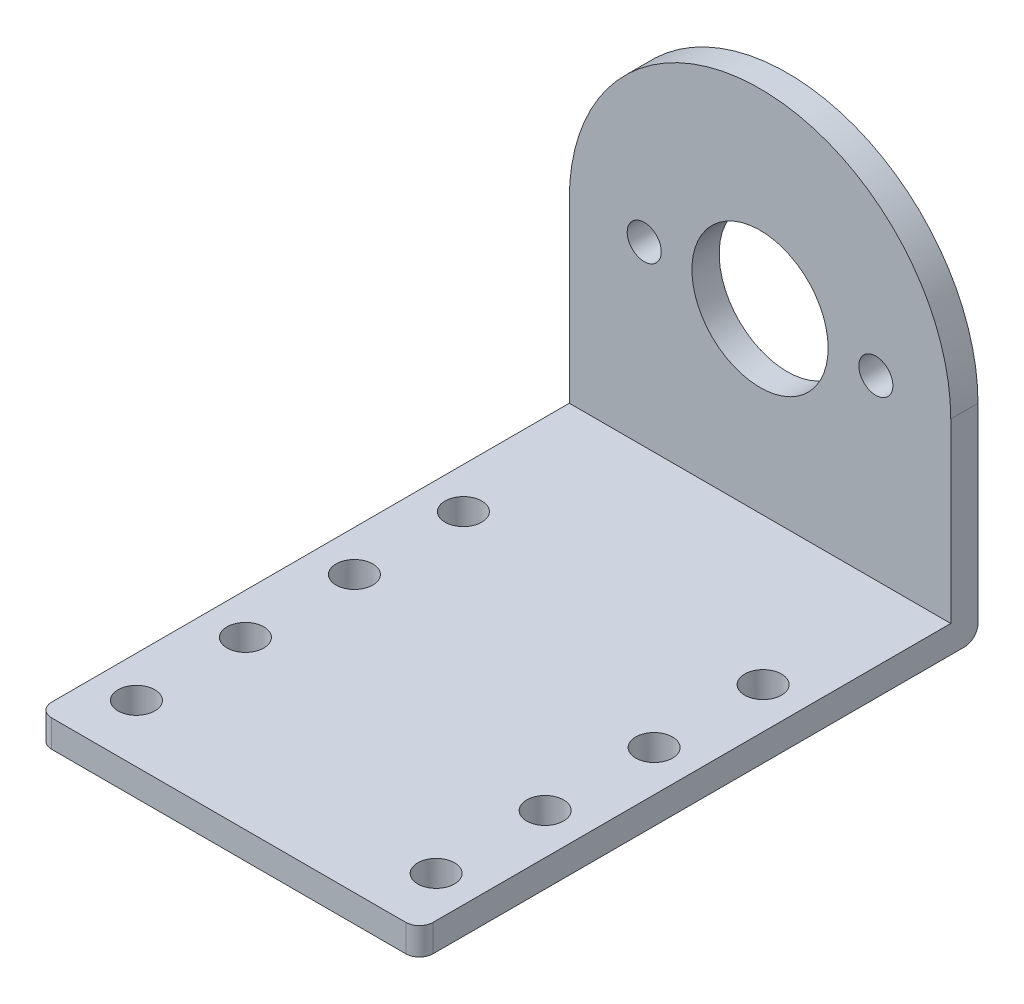
SolidWorks part; units mm, degrees
ref_plane "Front Plane" through (0, 0, 0) normal (0, 0, 1) x (1, 0, 0)
ref_plane "Top Plane" through (0, 0, 0) normal (0, 1, 0) x (1, 0, 0)
ref_plane "Right Plane" through (0, 0, 0) normal (1, 0, 0) x (0, 0, -1)
sketch "Sketch1" plane through (0, 0, 0) normal (0, 0, 1) x (1, 0, 0)
  line L0 (0, 0) -> (-8.5, 0) construction
  line L1 (0, 0) -> (8.5, 0) construction
  line L2 (-14, 0) -> (-14, -15)
  line L3 (14, 0) -> (14, -15)
  line L4 (14, -15) -> (-14, -15)
  arc A0 (14, 0) -> (-14, 0) centre (0, 0) ccw
  circle A1 centre (0, 0) radius 5
  circle A2 centre (-8.5, 0) radius 1.25
  circle A3 centre (8.5, 0) radius 1.25
  dimension "D1" = 28
  dimension "D2" = 10
  dimension "D3" = 2.5
  dimension "D5" = 2.5
  dimension "D4" = 8.5
  dimension "D6" = 8.5
  dimension "D7" = 15
extrude "Boss-Extrude1" add sketch "Sketch1" along normal blind 2
sketch "Sketch2" plane through (0, 0, 2) normal (0, 0, 1) x (1, 0, 0)
  line L0 (14, -15) -> (14, 0) construction
  line L1 (-14, -15) -> (14, -15)
  line L2 (-14, -15) -> (-14, -13)
  line L3 (-14, -13) -> (14, -13)
  line L4 (14, -15) -> (14, -13)
  dimension "D1" = 2
extrude "Boss-Extrude2" add sketch "Sketch2" along normal blind 39
fillet "Fillet1" radius 1 3 edges at (14, -14, 41) (-14, -14, 41) (0, -15, 0)
sketch "Sketch3" plane through (0, -13, 0) normal (0, 1, 0) x (1, 0, 0)
  line L0 (0, 0) -> (0, -12.7736) construction
  line L1 (-11, -12.7736) -> (0, -12.7736) construction
  line L2 (-11, -12.7736) -> (-11, -36.7736) construction
  line L3 (0, -12.7736) -> (0, -41) construction
  line L4 (13, -41) -> (-13, -41) construction
  circle A0 centre (-11, -12.7736) radius 1.35
  circle A1 centre (-11, -36.7736) radius 1.35
  circle A2 centre (11, -36.7736) radius 1.35
  circle A3 centre (11, -12.7736) radius 1.35
  circle A4 centre (-11, -20.7736) radius 1.35
  circle A5 centre (-11, -28.7736) radius 1.35
  circle A6 centre (11, -28.7736) radius 1.35
  circle A7 centre (11, -20.7736) radius 1.35
  dimension "D4" = 2.7
  dimension "D5" = 2.7
  dimension "D6" = 2.7
  dimension "D8" = 2.7
  dimension "D1" = 12.7736
  dimension "D2" = 11
  dimension "D3" = 24
  dimension "D7" = 8
  dimension "D9" = 8
extrude "Cut-Extrude1" cut sketch "Sketch3" against normal blind 17
